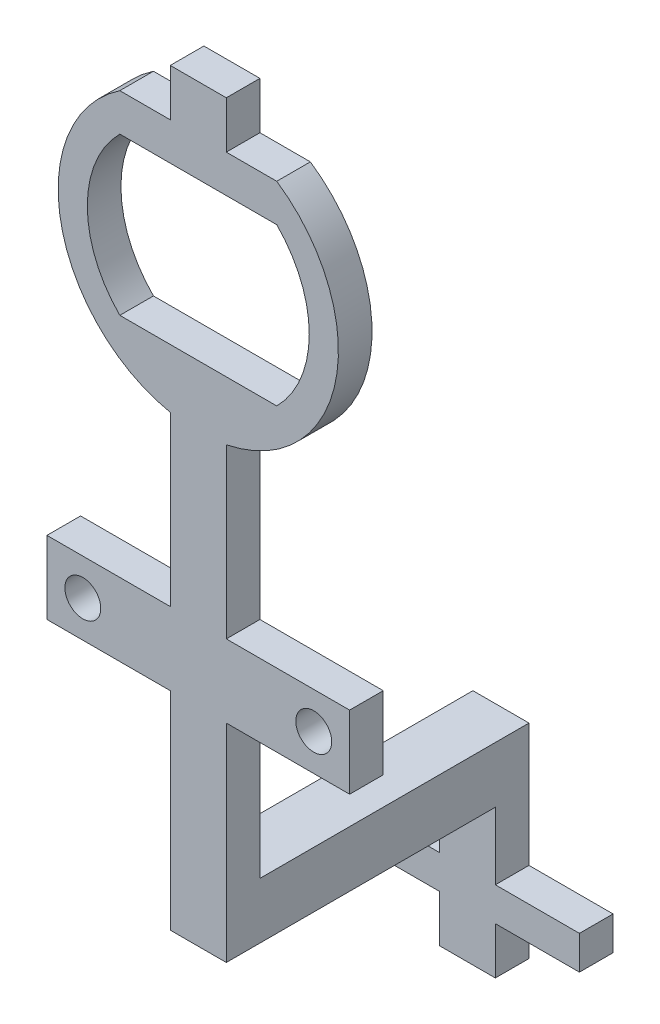
SolidWorks part; units mm, degrees
ref_plane "Front Plane" through (0, 0, 0) normal (0, 0, 1) x (1, 0, 0)
ref_plane "Top Plane" through (0, 0, 0) normal (0, 1, 0) x (1, 0, 0)
ref_plane "Right Plane" through (0, 0, 0) normal (1, 0, 0) x (0, 0, -1)
sketch "Sketch1" plane through (0, 0, 0) normal (0, 0, 1) x (1, 0, 0)
  line L0 (-7, 7.0007) -> (7, 7.0007)
  line L5 (-18.4746, 0) -> (14.4817, 0) construction
  line L6 (-7, -7.0007) -> (7, -7.0007)
  line L7 (-7, 10.3562) -> (7, 10.3562)
  line L8 (0, 0) -> (0, 29.3453) construction
  line L11 (-2.5, -7.0007) -> (2.3856, -7.0007)
  line L13 (2.5, -52.2474) -> (2.5, -12.2474)
  line L18 (-2.5, -52.2474) -> (-2.5, -12.2474)
  line L21 (2.5, -52.2474) -> (-2.5, -52.2474)
  arc A0 (-7, 7.0007) -> (-7, -7.0007) centre (0, 0) ccw
  arc A1 (7, -7.0007) -> (7, 7.0007) centre (0, 0) ccw
  arc A2 (-7, 10.3562) -> (-2.5, -12.2474) centre (0, 0) ccw
  arc A3 (2.5, -12.2474) -> (7, 10.3562) centre (0, 0) ccw
  dimension "D1" = 19.8
  dimension "D3" = 25
  dimension "D4" = 40
  dimension "D2" = 14
  dimension "D5" = 5
  dimension "D6" = 5.2467
  dimension "D7" = 4.5
extrude "Boss-Extrude1" add sketch "Sketch1" along normal blind 3 contours A3 L7 A2 A1 L6 A0 L0 region at (0, -15.9639, 0)
sketch "Sketch3" plane through (0, 0, 0) normal (0, 0, 1) x (1, 0, 0)
  line L0 (0, -46.1586) -> (0, 0.6217) construction
  line L1 (13.5, -27.2474) -> (-13.5, -27.2474)
  line L2 (13.5, -27.2474) -> (13.5, -33.7474)
  line L3 (13.5, -33.7474) -> (-13.5, -33.7474)
  line L4 (-13.5, -27.2474) -> (-13.5, -33.7474)
  line L5 (13.5, -27.2474) -> (-13.5, -33.7474) construction
  line L6 (13.5, -33.7474) -> (-13.5, -27.2474) construction
  line L8 (2.5, -52.2474) -> (-2.5, -52.2474) construction
  circle A0 centre (-10.3, -30.4974) radius 1.6
  circle A1 centre (10.3, -30.4974) radius 1.6
  point P0 (0, -30.4974)
  dimension "D4" = 3.2
  dimension "D5" = 3.2
  dimension "D6" = 3.25
  dimension "D1" = 27
  dimension "D2" = 6.5
  dimension "D3" = 18.5
sketch "Sketch4" plane through (0, 10.3562, 0) normal (0, 1, 0) x (1, 0, 0)
  line L0 (-7, 0) -> (7, 0) construction
  line L1 (2.5, -3) -> (-2.5, -3)
  line L2 (2.5, -3) -> (2.5, 0)
  line L3 (2.5, 0) -> (-2.5, 0)
  line L4 (-2.5, -3) -> (-2.5, 0)
  line L5 (2.5, -3) -> (-2.5, 0) construction
  line L6 (2.5, 0) -> (-2.5, -3) construction
  line L7 (-7, -3) -> (7, -3) construction
  line L8 (-7, -3) -> (-7, 0) construction
  point P0 (0, -1.5)
  point P14 (0, 0)
  dimension "D1" = 5
  dimension "D2" = 4.5
extrude "Boss-Extrude4" add sketch "Sketch3" along normal blind 3
extrude "Boss-Extrude3" add sketch "Sketch4" along normal blind 4.2
sketch "Sketch6" plane through (0, 0, 0) normal (0, 0, -1) x (-1, 0, 0)
  line L0 (2.5, -52.2474) -> (2.5, -33.7474) construction
  line L1 (-2.5, -52.2474) -> (2.5, -52.2474)
  line L2 (-2.5, -52.2474) -> (-2.5, -47.2474)
  line L3 (-2.5, -47.2474) -> (2.5, -47.2474)
  line L4 (2.5, -52.2474) -> (2.5, -47.2474)
  dimension "D1" = 5
extrude "Boss-Extrude5" add sketch "Sketch6" along normal blind 24
sketch "Sketch9" plane through (0, 0, -24) normal (0, 0, -1) x (-1, 0, 0)
  line L0 (2.5, -61.2438) -> (2.5, -65.4438)
  line L1 (-2.5, -52.2474) -> (2.5, -52.2474)
  line L2 (-2.5, -52.2474) -> (-2.5, -58.2438)
  line L3 (-2.5, -65.4438) -> (2.5, -65.4438)
  line L4 (2.5, -52.2474) -> (2.5, -58.2438)
  line L5 (10, -58.2438) -> (2.5, -58.2438)
  line L6 (10, -58.2438) -> (10, -61.2438)
  line L7 (10, -61.2438) -> (2.5, -61.2438)
  line L8 (-10, -58.2438) -> (-10, -61.2438)
  line L9 (-2.5, -61.2438) -> (-2.5, -65.4438)
  line L10 (-2.5, -58.2438) -> (-10, -58.2438)
  line L11 (-2.5, -61.2438) -> (-10, -61.2438)
  line L12 (-2.5, 14.5562) -> (2.5, 14.5562) construction
  dimension "D1" = 80
  dimension "D2" = 4.2
  dimension "D3" = 20
  dimension "D4" = 5
  dimension "D5" = 3
extrude "Boss-Extrude6" add sketch "Sketch9" against normal blind 3
